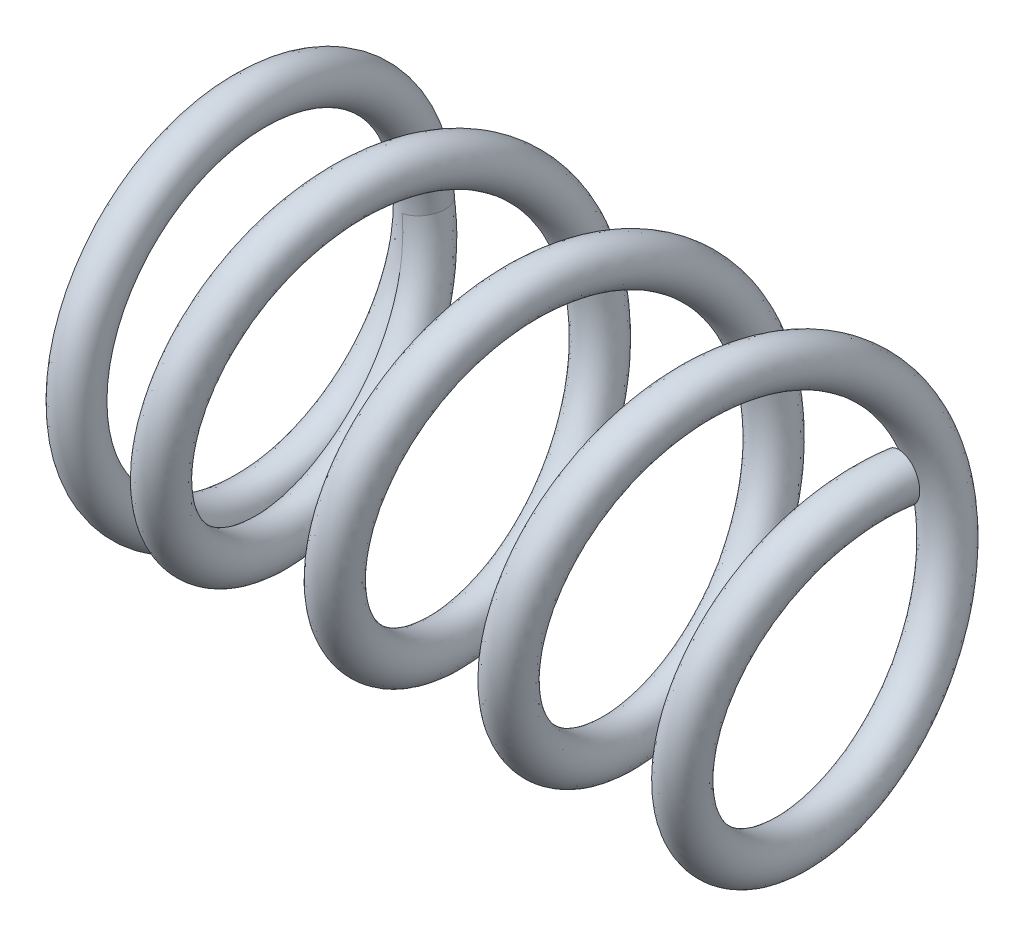
SolidWorks part; units mm, degrees
ref_plane "Vorne" through (0, 0, 0) normal (0, 0, 1) x (1, 0, 0)
ref_plane "Oben" through (0, 0, 0) normal (0, 1, 0) x (1, 0, 0)
ref_plane "Rechts" through (0, 0, 0) normal (1, 0, 0) x (0, 0, -1)
sketch "Skizze1" plane through (0, 0, 0) normal (1, 0, 0) x (0, 0, -1)
  circle A0 centre (0, 0) radius 8
  dimension "D1" = 16
curve "Spirale/Helix1" pitch 8 height 30 radius 8 left hand yes centre (0, 0, 0) axis (1, 0, 0) start towards (0, 0, -1)
ref_plane "Ebene1" through (0, 0, -8) normal (0.1572, -0.9876, 0) x (0.739, 0.1176, 0.6634)
sketch "Skizze3" plane through (0, 0, -8) normal (0.1572, -0.9876, 0) x (0.739, 0.1176, 0.6634)
  circle A0 centre (0, 0) radius 1
  dimension "D1" = 2
sweep "Austragung1" add profiles "Skizze3" path "Spirale/Helix1"
sketch "Skizze4" plane through (0, 0, -8) normal (0, -1, 0) x (0.7483, 0, 0.6634)
  line L0 (0, 0) -> (5.3072, 5.9862) construction
  line L1 (5.3072, 5.9862) -> (0.5746, 10.1819) construction
  line L2 (13.7498, -1.4989) -> (-3.1355, 13.4712) construction
  ellipse E0 centre (0, 0) end of major axis (-0.6634, -0.7483) minor radius 0.9876 construction
  ellipse E1 centre (0, 0) end of major axis (-0.6634, -0.7483) minor radius 0.9876
revolve "Rotation1" add sketch "Skizze4" angle 360 about L1
move or copy body "Körper-Verschieben/Kopieren1" [suppressed] bodies to move or copy 104
